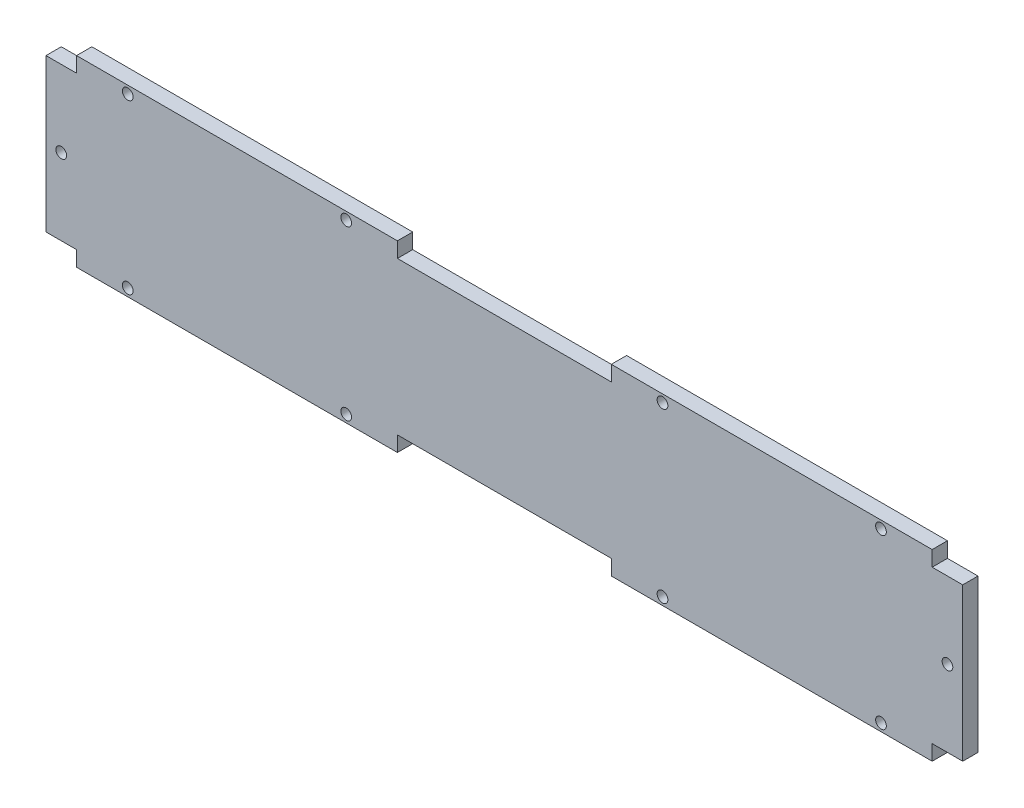
SolidWorks part; units mm, degrees
ref_plane "Front Plane" through (0, 0, 0) normal (0, 0, 1) x (1, 0, 0)
ref_plane "Top Plane" through (0, 0, 0) normal (0, 1, 0) x (1, 0, 0)
ref_plane "Right Plane" through (0, 0, 0) normal (1, 0, 0) x (0, 0, -1)
sketch "Sketch1" plane through (0, 0, 0) normal (0, 0, 1) x (1, 0, 0)
  line L0 (0, -1000) -> (0, 49000) construction
  line L1 (-140, -5) -> (-35, -5)
  line L2 (-140, -5) -> (-140, 0)
  line L3 (-140, 0) -> (-35, 0)
  line L4 (-35, -5) -> (-35, 0)
  line L5 (140, 0) -> (35, 0)
  line L6 (35, -5) -> (35, 0)
  line L7 (140, -5) -> (35, -5)
  line L8 (140, -5) -> (140, 0)
  line L9 (-1140, 25) -> (48860, 25) construction
  line L10 (-140, 0) -> (140, 0)
  line L11 (-140, 0) -> (-140, 50)
  line L12 (-140, 50) -> (140, 50)
  line L13 (140, 0) -> (140, 50)
  line L18 (140, 0) -> (150, 0)
  line L19 (140, 0) -> (140, 50)
  line L20 (140, 50) -> (140, -5)
  line L21 (140, 50) -> (150, 50)
  line L22 (-140, 0) -> (-150, 0)
  line L23 (-140, 0) -> (-140, 50)
  line L24 (-140, 50) -> (-150, 50)
  line L25 (-150, 0) -> (-150, 50)
  line L26 (150, 0) -> (150, 50)
  line L27 (140, 55) -> (140, 50)
  line L28 (140, 55) -> (35, 55)
  line L29 (35, 55) -> (35, 50)
  line L30 (140, 50) -> (35, 50)
  line L31 (-140, 50) -> (-35, 50)
  line L32 (-35, 55) -> (-35, 50)
  line L33 (-140, 55) -> (-35, 55)
  line L34 (-140, 55) -> (-140, 50)
  point P13 (0, 0)
  point P21 (-140, 25)
  dimension "D1" = 5
  dimension "D2" = 105
  dimension "D3" = 140
  dimension "D4" = 50
  dimension "D5" = 10
  dimension "D6" = 10
extrude "Boss-Extrude1" add sketch "Sketch1" along normal blind 5 contours L10 L0 L12 L11 L3 | L0 L10 L5 L13 L12 | L2 L1 L4 L3 | L5 L6 L7 L8 | L23 L22 L25 L24 | L19 L18 L26 L21 | L31 L32 L33 L34 | L30 L29 L28 L27 region at (0, 25, 0)
sketch "Sketch2" plane through (0, 0, 5) normal (0, 0, 1) x (1, 0, 0)
  line L0 (-87.5, -1005) -> (-87.5, 48995) construction
  line L1 (-140, -5) -> (-35, -5) construction
  line L3 (-35, -5) -> (-140, -5) construction
  line L4 (-35, -5) -> (-35, 0) construction
  line L5 (-35, 0) -> (-140, 0) construction
  line L6 (-140, -5) -> (-140, 0) construction
  line L7 (-140, -5) -> (-140, 0) construction
  line L8 (0, -1000) -> (0, 49000) construction
  line L9 (-140, -5) -> (-140, 0) construction
  line L10 (-1150, 25) -> (48850, 25) construction
  line L11 (-150, 0) -> (-150, 50) construction
  circle A0 centre (-123.25, -2.5) radius 1.75
  circle A1 centre (-51.75, -2.5) radius 1.75
  circle A2 centre (51.75, -2.5) radius 1.75
  circle A3 centre (123.25, -2.5) radius 1.75
  circle A4 centre (123.25, 52.5) radius 1.75
  circle A5 centre (51.75, 52.5) radius 1.75
  circle A6 centre (-51.75, 52.5) radius 1.75
  circle A7 centre (-123.25, 52.5) radius 1.75
  point P7 (-87.5, -5)
  point P17 (-140, -2.5)
  point P18 (-125, -2.5)
  point P33 (-150, 25)
  dimension "D1" = 3.5
  dimension "D2" = 15
extrude "Cut-Extrude1" cut sketch "Sketch2" against normal blind 5
sketch "Sketch3" plane through (0, 0, 5) normal (0, 0, 1) x (1, 0, 0)
  line L0 (-150, 0) -> (-150, 50) construction
  line L1 (0, -1000) -> (0, 49000) construction
  circle A0 centre (-145, 25) radius 1.75
  circle A1 centre (145, 25) radius 1.75
  point P5 (-150, 25)
  dimension "D1" = 3.5
  dimension "D2" = 5
extrude "Cut-Extrude2" cut sketch "Sketch3" against normal blind 10
